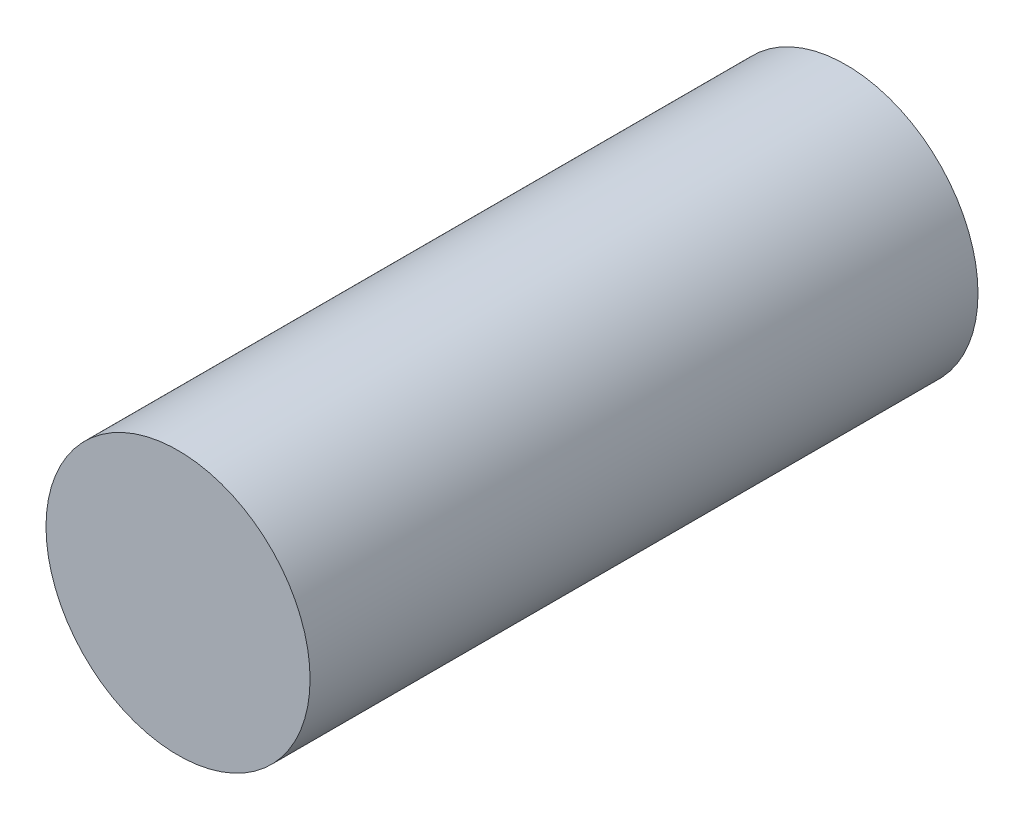
SolidWorks part; units mm, degrees
ref_plane "Plan de face" through (0, 0, 0) normal (0, 0, 1) x (1, 0, 0)
ref_plane "Plan de dessus" through (0, 0, 0) normal (0, 1, 0) x (1, 0, 0)
ref_plane "Plan de droite" through (0, 0, 0) normal (1, 0, 0) x (0, 0, -1)
sketch "Main-Sketch" plane through (0, 0, 0) normal (0, 0, 1) x (1, 0, 0)
  circle A0 centre (-14.218, 13.7133) radius 8.5
  dimension "D1" = 17
extrude "Main-Extrusion" add sketch "Main-Sketch" along normal blind 43
